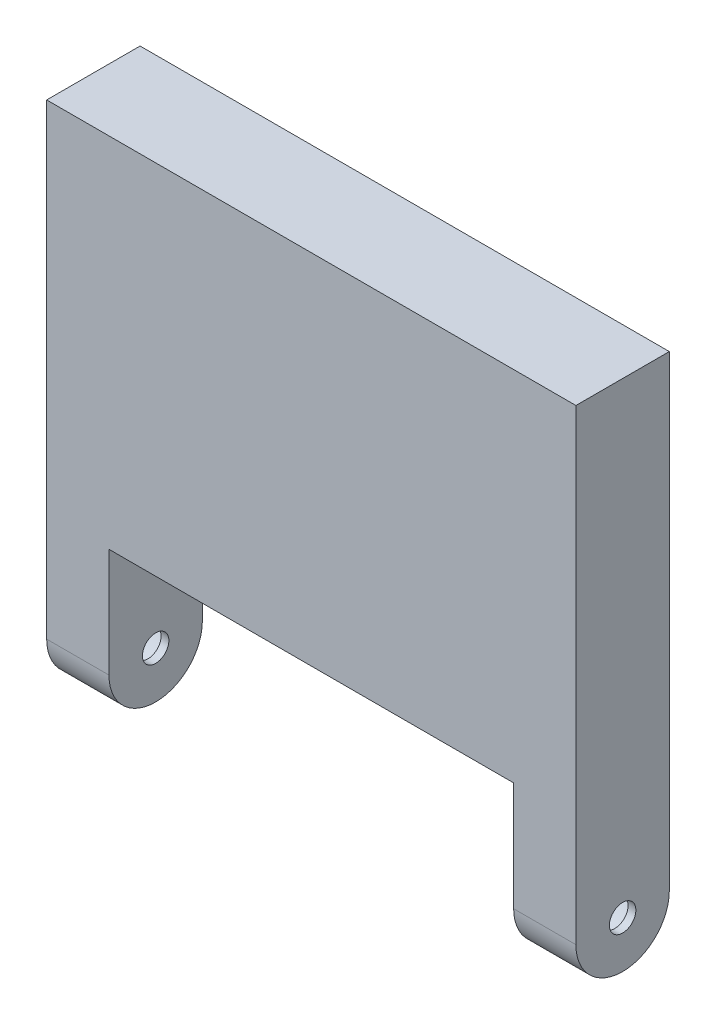
SolidWorks part; units mm, degrees
ref_plane "Front Plane" through (0, 0, 0) normal (0, 0, 1) x (1, 0, 0)
ref_plane "Top Plane" through (0, 0, 0) normal (0, 1, 0) x (1, 0, 0)
ref_plane "Right Plane" through (0, 0, 0) normal (1, 0, 0) x (0, 0, -1)
sketch "Sketch1" plane through (0, 0, 0) normal (0, 0, 1) x (1, 0, 0)
  line L0 (-276.0597, 0) -> (276.0597, 0) construction
  line L1 (-170, -30) -> (-170, 300)
  line L2 (-170, 300) -> (0, 300)
  line L3 (-170, -30) -> (-130, -30)
  line L4 (0, -283.5322) -> (0, 283.5322) construction
  line L5 (-130, -30) -> (-130, 70)
  line L6 (-130, 70) -> (0, 70)
  line L7 (-238.394, -30) -> (238.394, -30) construction
  line L8 (-135, 75) -> (0, 75)
  line L9 (-135, -25) -> (-135, 75)
  line L10 (-165, -25) -> (-135, -25)
  line L11 (-165, -25) -> (-165, 295)
  line L12 (-165, 295) -> (0, 295)
  point P10 (0, -30)
  dimension "D1" = 340
  dimension "D2" = 100
  dimension "D3" = 60
  dimension "D4" = 300
  dimension "D5" = 260
  dimension "D6" = 5
sketch "Sketch3" plane through (0, 0, 0) normal (1, 0, 0) x (0, 0, -1)
  line L0 (0, 0) -> (0, -30) construction
  line L1 (0, -283.5322) -> (0, 283.5322) construction
  line L2 (-30, 0) -> (-30, 300)
  line L3 (-30, 300) -> (30, 300)
  line L4 (30, 300) -> (30, 0)
  line L5 (30, 70) -> (-30, 70)
  line L6 (25, 295) -> (25, 0)
  line L7 (-25, 0) -> (-25, 295)
  line L8 (-25, 295) -> (25, 295)
  line L9 (30, 75) -> (-30, 75)
  arc A0 (-30, 0) -> (30, 0) centre (0, 0) ccw
  arc A1 (-25, 0) -> (25, 0) centre (0, 0) ccw
  dimension "D2" = 5
  dimension "D1" = 5
extrude "Boss-Extrude1" add sketch "Sketch3" along normal up to vertex (-165 mm away) from vertex contours L9 L6 L8 L7 | L9 L4 L3 L2 L7 L8 L6 | L6 L9 L7 L5 | L4 L9 L6 L5 | L7 L9 L2 L5 | L0 A1 L7 L5 L2 A0 | A1 L0 A0 L4 L5 L6 | L7 A1 L6 L5 region at (0, -18.4159, -18.4159) region at (0, -27.5, 1.044) region at (0, 25.0088, 0) region at (0, 72.5, 0) region at (0, 72.5, 27.5) region at (0, 72.5, -27.5) region at (0, 77.3286, 27.5) region at (0, 185, 0) up to point (-165, -25, 0) starting at point (-170, -30, 0)
extrude "Boss-Extrude2" add sketch "Sketch3<4>" along normal up to vertex (-135 mm away) from vertex contours L9 L4 L3 L2 L7 L8 L6 | L7 L9 L2 L5 | L0 A1 L7 L5 L2 A0 | L4 L9 L6 L5 | A1 L0 A0 L4 L5 L6 region at (0, -18.4159, -18.4159) region at (0, -27.5, 1.044) region at (0, 72.5, 27.5) region at (0, 72.5, -27.5) region at (0, 77.3286, 27.5) up to point (-135, -25, 0) starting at point (-165, -25, 0)
sketch "Sketch3<4>" plane through (0, 0, 0) normal (1, 0, 0) x (0, 0, -1) same geometry as "Sketch3"
extrude "Boss-Extrude3" add sketch "Sketch3<5>" along normal up to vertex (-130 mm away) from vertex contours L9 L4 L3 L2 L7 L8 L6 | L7 L9 L2 L5 | L4 L9 L6 L5 | L6 L9 L7 L5 | A1 L0 A0 L4 L5 L6 | L7 A1 L6 L5 | L0 A1 L7 L5 L2 A0 region at (0, -18.4159, -18.4159) region at (0, -27.5, 1.044) region at (0, 25.0088, 0) region at (0, 72.5, 0) region at (0, 72.5, 27.5) region at (0, 72.5, -27.5) region at (0, 77.3286, 27.5) up to point (-130, -30, 0) starting at point (-135, -25, 0)
sketch "Sketch3<5>" plane through (0, 0, 0) normal (1, 0, 0) x (0, 0, -1) same geometry as "Sketch3"
extrude "Boss-Extrude4" add sketch "Sketch3<6>" along normal up to surface from vertex contours L9 L4 L3 L2 L7 L8 L6 | L7 L9 L2 L5 | L6 L9 L7 L5 | L4 L9 L6 L5 region at (0, 72.5, 27.5) region at (0, 187.5, 27.6714) region at (0, 72.5, 0) region at (0, 72.5, -27.5) up to plane "Right Plane" starting at point (-130, 70, 0)
sketch "Sketch3<6>" plane through (0, 0, 0) normal (1, 0, 0) x (0, 0, -1) same geometry as "Sketch3"
sketch "Sketch6" plane through (0, 0, 0) normal (1, 0, 0) x (0, 0, -1)
  line L0 (0, -283.5322) -> (0, 283.5322) construction
  circle A0 centre (0, 0) radius 8.5
  dimension "D1" = 17
extrude "Cut-Extrude1" cut sketch "Sketch6" against normal through all
mirror "Mirror5" about plane through (0, 0, 0) normal (1, 0, 0) of bodies 108 104
equation "\"D2@Sketch3\"=\"D1@Sketch3\""
